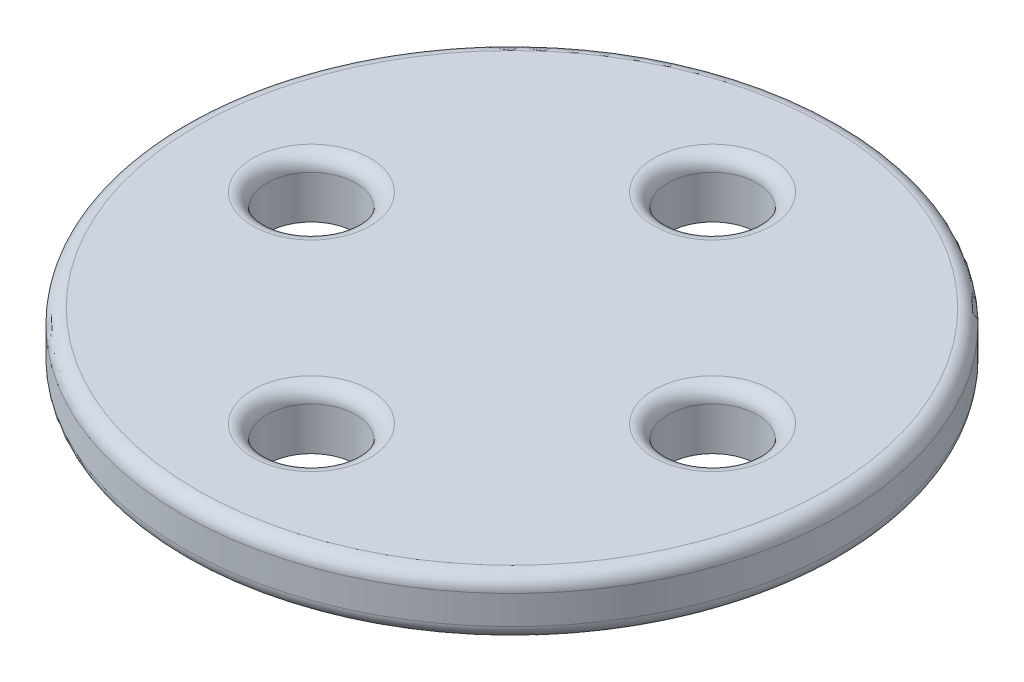
SolidWorks part; units mm, degrees
other "graphite_1"
other "white_2"
other "white_3"
other "white_10"
other "white_7"
other "white_6"
other "blue_2"
ref_plane "Front Plane" through (0, 0, 0) normal (0, 0, 1) x (1, 0, 0)
ref_plane "Top Plane" through (0, 0, 0) normal (0, 1, 0) x (1, 0, 0)
ref_plane "Right Plane" through (0, 0, 0) normal (1, 0, 0) x (0, 0, -1)
sketch "Sketch1" plane through (0, 0, 0) normal (0, 1, 0) x (1, 0, 0)
  line L0 (0, 7) -> (0, 0) construction
  circle A0 centre (0, 0) radius 11.5
  circle A1 centre (0, 7) radius 1.55
  circle A2 centre (7, 0) radius 1.55
  circle A3 centre (0, -7) radius 1.55
  circle A4 centre (-7, 0) radius 1.55
  point P14 (0, 0)
  dimension "D1" = 23
  dimension "D2" = 3.1
  dimension "D3" = 7
  dimension "D4" = 4
extrude "Boss-Extrude1" add sketch "Sketch1" along normal blind 2
fillet "Fillet1" radius 0.5 6 edges at (-7, 2, 1.55) (7, 2, 1.55) (0, 2, 11.5) (0, 2, -5.45) (0, 2, 8.55) (0, 0, 11.5)
sketch "Sketch2" [suppressed] plane through (0, 2, 0) normal (0, 1, 0) x (1, 0, 0)
  line L0 (-2.4749, -2.4749) -> (2.4749, 2.4749) construction
  line L3 (-4.2426, -0.7071) -> (0.7071, 4.2426) construction
  line L4 (-0.7071, -4.2426) -> (4.2426, 0.7071) construction
  line L5 (0, 0) -> (23.072, 0) construction
  line L6 (-6.364, -2.1213) -> (-2.1213, -6.364) construction
  line L7 (-2.1213, -6.364) -> (6.364, 2.1213) construction
  line L8 (6.364, 2.1213) -> (2.1213, 6.364) construction
  line L9 (2.1213, 6.364) -> (-6.364, -2.1213) construction
  line L10 (-6.364, -2.1213) -> (6.364, 2.1213) construction
  line L11 (2.1213, 6.364) -> (6.364, 2.1213)
  line L12 (6.364, 2.1213) -> (4.9497, 0.7071)
  line L13 (2.1213, 6.364) -> (0.7071, 4.9497)
  line L14 (-6.364, -2.1213) -> (-4.9497, -0.7071)
  line L15 (-6.364, -2.1213) -> (-2.1213, -6.364)
  line L16 (-2.1213, -6.364) -> (-0.7071, -4.9497)
  circle A0 centre (-7, 0) radius 2.75 construction
  circle A1 centre (0, 7) radius 2.75 construction
  circle A2 centre (7, 0) radius 2.75 construction
  circle A3 centre (0, -7) radius 2.75 construction
  arc A6 (-4.2426, -0.7071) -> (-0.7071, -4.2426) centre (-2.4749, -2.4749) ccw construction
  arc A7 (4.2426, 0.7071) -> (0.7071, 4.2426) centre (2.4749, 2.4749) ccw construction
  circle A8 centre (0, 0) radius 5 construction
  arc A10 (-0.7071, -4.9497) -> (4.9497, 0.7071) centre (0, 0) ccw
  arc A12 (0.7071, 4.9497) -> (-4.9497, -0.7071) centre (0, 0) ccw
  point P13 (0, 0)
  dimension "D1" = 5.5
  dimension "D2" = 12
  dimension "D3" = 5
  dimension "D7" = 10
  dimension "D4" = 45
  dimension "D5" = 6
  dimension "D6" = 12
extrude "Cable hole" [suppressed] cut sketch "Sketch2" against normal through all
fillet "Fillet2" [suppressed] radius 1
sketch "GL_F_side_blue" plane through (0, 0, 0) normal (0, 1, 0) x (1, 0, 0)
  line L0 (4.1012, -5.7912) -> (3.5426, -5.2326)
  line L1 (3.5426, -5.2326) -> (4.0376, -4.7376)
  line L2 (4.0376, -4.7376) -> (3.7477, -4.4477)
  line L3 (3.7477, -4.4477) -> (3.2527, -4.9427)
  line L4 (3.2527, -4.9427) -> (2.6941, -4.3841)
  line L5 (2.6941, -4.3841) -> (3.1891, -3.8891)
  line L6 (3.1891, -3.8891) -> (1.2092, -1.9092)
  line L7 (1.2092, -1.9092) -> (1.3233, -1.795)
  line L8 (1.3233, -1.795) -> (-1.795, -1.795)
  line L9 (-1.795, -1.795) -> (-1.795, 1.3233)
  line L10 (-1.795, 1.3233) -> (-1.9092, 1.2092)
  line L11 (-1.9092, 1.2092) -> (-4.852, 4.1519)
  line L12 (-4.852, 4.1519) -> (-4.7161, 4.1794)
  line L13 (-4.7161, 4.1794) -> (-4.5701, 4.2398)
  line L14 (-4.5701, 4.2398) -> (-4.3805, 4.3805)
  line L15 (-4.3805, 4.3805) -> (-4.2398, 4.5701)
  line L16 (-4.2398, 4.5701) -> (-4.1794, 4.7161)
  line L17 (-4.1794, 4.7161) -> (-4.1519, 4.852)
  line L18 (-4.1519, 4.852) -> (-1.2092, 1.9092)
  line L19 (-1.2092, 1.9092) -> (-1.3233, 1.795)
  line L20 (-1.3233, 1.795) -> (1.3233, 1.795)
  line L21 (1.3233, 1.795) -> (1.2092, 1.9092)
  line L22 (1.2092, 1.9092) -> (5.6637, 6.3638)
  line L23 (5.6637, 6.3638) -> (5.6872, 6.2571)
  line L24 (5.6872, 6.2571) -> (5.7514, 6.1022)
  line L25 (5.7514, 6.1022) -> (5.9008, 5.9008)
  line L26 (5.9008, 5.9008) -> (6.1022, 5.7514)
  line L27 (6.1022, 5.7514) -> (6.2571, 5.6872)
  line L28 (6.2571, 5.6872) -> (6.3638, 5.6637)
  line L29 (6.3638, 5.6637) -> (1.9092, 1.2092)
  line L30 (1.9092, 1.2092) -> (1.795, 1.3233)
  line L31 (1.795, 1.3233) -> (1.795, -1.3233)
  line L32 (1.795, -1.3233) -> (1.9092, -1.2092)
  line L33 (1.9092, -1.2092) -> (3.8891, -3.1891)
  line L34 (3.8891, -3.1891) -> (4.3841, -2.6941)
  line L35 (4.3841, -2.6941) -> (4.9427, -3.2527)
  line L36 (4.9427, -3.2527) -> (4.4477, -3.7477)
  line L37 (4.4477, -3.7477) -> (4.7376, -4.0376)
  line L38 (4.7376, -4.0376) -> (5.2326, -3.5426)
  line L39 (5.2326, -3.5426) -> (5.7912, -4.1012)
  line L40 (5.7912, -4.1012) -> (5.2962, -4.5962)
  line L41 (5.2962, -4.5962) -> (6.9933, -6.2933)
  line L42 (6.9933, -6.2933) -> (6.2933, -6.9933)
  line L43 (6.2933, -6.9933) -> (4.5962, -5.2962)
  line L44 (4.5962, -5.2962) -> (4.1012, -5.7912)
  line L45 (-0.2962, 0.7941) -> (-0.2962, 0.9029)
  line L46 (-0.2962, 0.9029) -> (-0.3174, 1.0096)
  line L47 (-0.3174, 1.0096) -> (-0.359, 1.1102)
  line L48 (-0.359, 1.1102) -> (-0.4195, 1.2006)
  line L49 (-0.4195, 1.2006) -> (-0.4964, 1.2776)
  line L50 (-0.4964, 1.2776) -> (-0.5869, 1.338)
  line L51 (-0.5869, 1.338) -> (-0.6874, 1.3797)
  line L52 (-0.6874, 1.3797) -> (-0.7941, 1.4009)
  line L53 (-0.7941, 1.4009) -> (-0.9029, 1.4009)
  line L54 (-0.9029, 1.4009) -> (-1.0096, 1.3797)
  line L55 (-1.0096, 1.3797) -> (-1.1102, 1.338)
  line L56 (-1.1102, 1.338) -> (-1.2006, 1.2776)
  line L57 (-1.2006, 1.2776) -> (-1.2776, 1.2006)
  line L58 (-1.2776, 1.2006) -> (-1.338, 1.1102)
  line L59 (-1.338, 1.1102) -> (-1.3797, 1.0096)
  line L60 (-1.3797, 1.0096) -> (-1.4009, 0.9029)
  line L61 (-1.4009, 0.9029) -> (-1.4009, 0.7941)
  line L62 (-1.4009, 0.7941) -> (-1.3797, 0.6874)
  line L63 (-1.3797, 0.6874) -> (-1.338, 0.5869)
  line L64 (-1.338, 0.5869) -> (-1.2776, 0.4964)
  line L65 (-1.2776, 0.4964) -> (-1.2006, 0.4195)
  line L66 (-1.2006, 0.4195) -> (-1.1102, 0.359)
  line L67 (-1.1102, 0.359) -> (-1.0096, 0.3174)
  line L68 (-1.0096, 0.3174) -> (-0.9029, 0.2962)
  line L69 (-0.9029, 0.2962) -> (-0.7941, 0.2962)
  line L70 (-0.7941, 0.2962) -> (-0.6874, 0.3174)
  line L71 (-0.6874, 0.3174) -> (-0.5869, 0.359)
  line L72 (-0.5869, 0.359) -> (-0.4964, 0.4195)
  line L73 (-0.4964, 0.4195) -> (-0.4195, 0.4964)
  line L74 (-0.4195, 0.4964) -> (-0.359, 0.5869)
  line L75 (-0.359, 0.5869) -> (-0.3174, 0.6874)
  line L76 (-0.3174, 0.6874) -> (-0.2962, 0.7941)
extrude "GL_F_side_blue_raised" add sketch "GL_F_side_blue" along normal blind 0.6 from offset 0.6 separate body offset against normal yes
sketch "GL_F_side_white" plane through (0, 0, 0) normal (0, 1, 0) x (1, 0, 0)
  line L0 (-5.628, -6.3839) -> (-5.6958, -6.4665)
  line L1 (-5.6958, -6.4665) -> (-5.7783, -6.5342)
  line L2 (-5.7783, -6.5342) -> (-5.8726, -6.5846)
  line L3 (-5.8726, -6.5846) -> (-5.9748, -6.6156)
  line L4 (-5.9748, -6.6156) -> (-6.0811, -6.6261)
  line L5 (-6.0811, -6.6261) -> (-6.1874, -6.6156)
  line L6 (-6.1874, -6.6156) -> (-6.2897, -6.5846)
  line L7 (-6.2897, -6.5846) -> (-6.3839, -6.5342)
  line L8 (-6.3839, -6.5342) -> (-6.4665, -6.4665)
  line L9 (-6.4665, -6.4665) -> (-6.5342, -6.3839)
  line L10 (-6.5342, -6.3839) -> (-6.5846, -6.2897)
  line L11 (-6.5846, -6.2897) -> (-6.6156, -6.1874)
  line L12 (-6.6156, -6.1874) -> (-6.6261, -6.0811)
  line L13 (-6.6261, -6.0811) -> (-6.6156, -5.9748)
  line L14 (-6.6156, -5.9748) -> (-6.5846, -5.8726)
  line L15 (-6.5846, -5.8726) -> (-6.5342, -5.7783)
  line L16 (-6.5342, -5.7783) -> (-6.4665, -5.6958)
  line L17 (-6.4665, -5.6958) -> (-6.3839, -5.628)
  line L18 (-6.3839, -5.628) -> (-6.2897, -5.5776)
  line L19 (-6.2897, -5.5776) -> (-6.1874, -5.5466)
  line L20 (-6.1874, -5.5466) -> (-6.0811, -5.5361)
  line L21 (-6.0811, -5.5361) -> (-5.9748, -5.5466)
  line L22 (-5.9748, -5.5466) -> (-5.8726, -5.5776)
  line L23 (-5.8726, -5.5776) -> (-5.7783, -5.628)
  line L24 (-5.7783, -5.628) -> (-5.6958, -5.6958)
  line L25 (-5.6958, -5.6958) -> (-5.628, -5.7783)
  line L26 (-5.628, -5.7783) -> (-5.5776, -5.8726)
  line L27 (-5.5776, -5.8726) -> (-5.5466, -5.9748)
  line L28 (-5.5466, -5.9748) -> (-5.5361, -6.0811)
  line L29 (-5.5361, -6.0811) -> (-5.5466, -6.1874)
  line L30 (-5.5466, -6.1874) -> (-5.5776, -6.2897)
  line L31 (-5.5776, -6.2897) -> (-5.628, -6.3839)
  line L32 (-3.7895, -4.5454) -> (-3.8573, -4.628)
  line L33 (-3.8573, -4.628) -> (-3.9399, -4.6958)
  line L34 (-3.9399, -4.6958) -> (-4.0341, -4.7461)
  line L35 (-4.0341, -4.7461) -> (-4.1363, -4.7771)
  line L36 (-4.1363, -4.7771) -> (-4.2426, -4.7876)
  line L37 (-4.2426, -4.7876) -> (-4.349, -4.7771)
  line L38 (-4.349, -4.7771) -> (-4.4512, -4.7461)
  line L39 (-4.4512, -4.7461) -> (-4.5454, -4.6958)
  line L40 (-4.5454, -4.6958) -> (-4.628, -4.628)
  line L41 (-4.628, -4.628) -> (-4.6958, -4.5454)
  line L42 (-4.6958, -4.5454) -> (-4.7461, -4.4512)
  line L43 (-4.7461, -4.4512) -> (-4.7771, -4.349)
  line L44 (-4.7771, -4.349) -> (-4.7876, -4.2426)
  line L45 (-4.7876, -4.2426) -> (-4.7771, -4.1363)
  line L46 (-4.7771, -4.1363) -> (-4.7461, -4.0341)
  line L47 (-4.7461, -4.0341) -> (-4.6958, -3.9399)
  line L48 (-4.6958, -3.9399) -> (-4.628, -3.8573)
  line L49 (-4.628, -3.8573) -> (-4.5454, -3.7895)
  line L50 (-4.5454, -3.7895) -> (-4.4512, -3.7391)
  line L51 (-4.4512, -3.7391) -> (-4.349, -3.7081)
  line L52 (-4.349, -3.7081) -> (-4.2426, -3.6977)
  line L53 (-4.2426, -3.6977) -> (-4.1363, -3.7081)
  line L54 (-4.1363, -3.7081) -> (-4.0341, -3.7391)
  line L55 (-4.0341, -3.7391) -> (-3.9399, -3.7895)
  line L56 (-3.9399, -3.7895) -> (-3.8573, -3.8573)
  line L57 (-3.8573, -3.8573) -> (-3.7895, -3.9399)
  line L58 (-3.7895, -3.9399) -> (-3.7391, -4.0341)
  line L59 (-3.7391, -4.0341) -> (-3.7081, -4.1363)
  line L60 (-3.7081, -4.1363) -> (-3.6977, -4.2426)
  line L61 (-3.6977, -4.2426) -> (-3.7081, -4.349)
  line L62 (-3.7081, -4.349) -> (-3.7391, -4.4512)
  line L63 (-3.7391, -4.4512) -> (-3.7895, -4.5454)
  line L64 (-0.3954, 0.5458) -> (-0.4632, 0.4632)
  line L65 (-0.4632, 0.4632) -> (-0.5458, 0.3954)
  line L66 (-0.5458, 0.3954) -> (-0.64, 0.345)
  line L67 (-0.64, 0.345) -> (-0.7422, 0.314)
  line L68 (-0.7422, 0.314) -> (-0.8485, 0.3036)
  line L69 (-0.8485, 0.3036) -> (-0.9548, 0.314)
  line L70 (-0.9548, 0.314) -> (-1.0571, 0.345)
  line L71 (-1.0571, 0.345) -> (-1.1513, 0.3954)
  line L72 (-1.1513, 0.3954) -> (-1.2339, 0.4632)
  line L73 (-1.2339, 0.4632) -> (-1.3017, 0.5458)
  line L74 (-1.3017, 0.5458) -> (-1.352, 0.64)
  line L75 (-1.352, 0.64) -> (-1.383, 0.7422)
  line L76 (-1.383, 0.7422) -> (-1.3935, 0.8485)
  line L77 (-1.3935, 0.8485) -> (-1.383, 0.9548)
  line L78 (-1.383, 0.9548) -> (-1.352, 1.0571)
  line L79 (-1.352, 1.0571) -> (-1.3017, 1.1513)
  line L80 (-1.3017, 1.1513) -> (-1.2339, 1.2339)
  line L81 (-1.2339, 1.2339) -> (-1.1513, 1.3017)
  line L82 (-1.1513, 1.3017) -> (-1.0571, 1.352)
  line L83 (-1.0571, 1.352) -> (-0.9548, 1.383)
  line L84 (-0.9548, 1.383) -> (-0.8485, 1.3935)
  line L85 (-0.8485, 1.3935) -> (-0.7422, 1.383)
  line L86 (-0.7422, 1.383) -> (-0.64, 1.352)
  line L87 (-0.64, 1.352) -> (-0.5458, 1.3017)
  line L88 (-0.5458, 1.3017) -> (-0.4632, 1.2339)
  line L89 (-0.4632, 1.2339) -> (-0.3954, 1.1513)
  line L90 (-0.3954, 1.1513) -> (-0.345, 1.0571)
  line L91 (-0.345, 1.0571) -> (-0.314, 0.9548)
  line L92 (-0.314, 0.9548) -> (-0.3036, 0.8485)
  line L93 (-0.3036, 0.8485) -> (-0.314, 0.7422)
  line L94 (-0.314, 0.7422) -> (-0.345, 0.64)
  line L95 (-0.345, 0.64) -> (-0.3954, 0.5458)
  line L96 (-4.3876, 4.3876) -> (-4.5081, 4.2887)
  line L97 (-4.5081, 4.2887) -> (-4.6455, 4.2153)
  line L98 (-4.6455, 4.2153) -> (-4.7947, 4.17)
  line L99 (-4.7947, 4.17) -> (-4.9497, 4.1548)
  line L100 (-4.9497, 4.1548) -> (-5.1048, 4.17)
  line L101 (-5.1048, 4.17) -> (-5.254, 4.2153)
  line L102 (-5.254, 4.2153) -> (-5.3914, 4.2887)
  line L103 (-5.3914, 4.2887) -> (-5.5119, 4.3876)
  line L104 (-5.5119, 4.3876) -> (-5.6107, 4.5081)
  line L105 (-5.6107, 4.5081) -> (-5.6842, 4.6455)
  line L106 (-5.6842, 4.6455) -> (-5.7294, 4.7947)
  line L107 (-5.7294, 4.7947) -> (-5.7447, 4.9497)
  line L108 (-5.7447, 4.9497) -> (-5.7294, 5.1048)
  line L109 (-5.7294, 5.1048) -> (-5.6842, 5.254)
  line L110 (-5.6842, 5.254) -> (-5.6107, 5.3914)
  line L111 (-5.6107, 5.3914) -> (-5.5119, 5.5119)
  line L112 (-5.5119, 5.5119) -> (-5.3914, 5.6107)
  line L113 (-5.3914, 5.6107) -> (-5.254, 5.6842)
  line L114 (-5.254, 5.6842) -> (-5.1048, 5.7294)
  line L115 (-5.1048, 5.7294) -> (-4.9497, 5.7447)
  line L116 (-4.9497, 5.7447) -> (-4.7947, 5.7294)
  line L117 (-4.7947, 5.7294) -> (-4.6455, 5.6842)
  line L118 (-4.6455, 5.6842) -> (-4.5081, 5.6107)
  line L119 (-4.5081, 5.6107) -> (-4.3876, 5.5119)
  line L120 (-4.3876, 5.5119) -> (-4.2887, 5.3914)
  line L121 (-4.2887, 5.3914) -> (-4.2153, 5.254)
  line L122 (-4.2153, 5.254) -> (-4.17, 5.1048)
  line L123 (-4.17, 5.1048) -> (-4.1548, 4.9497)
  line L124 (-4.1548, 4.9497) -> (-4.17, 4.7947)
  line L125 (-4.17, 4.7947) -> (-4.2153, 4.6455)
  line L126 (-4.2153, 4.6455) -> (-4.2887, 4.5081)
  line L127 (-4.2887, 4.5081) -> (-4.3876, 4.3876)
  line L128 (7.1029, 5.9079) -> (6.9748, 5.8028)
  line L129 (6.9748, 5.8028) -> (6.8287, 5.7247)
  line L130 (6.8287, 5.7247) -> (6.6702, 5.6766)
  line L131 (6.6702, 5.6766) -> (6.5054, 5.6604)
  line L132 (6.5054, 5.6604) -> (6.3405, 5.6766)
  line L133 (6.3405, 5.6766) -> (6.182, 5.7247)
  line L134 (6.182, 5.7247) -> (6.0359, 5.8028)
  line L135 (6.0359, 5.8028) -> (5.9079, 5.9079)
  line L136 (5.9079, 5.9079) -> (5.8028, 6.0359)
  line L137 (5.8028, 6.0359) -> (5.7247, 6.182)
  line L138 (5.7247, 6.182) -> (5.6766, 6.3405)
  line L139 (5.6766, 6.3405) -> (5.6604, 6.5054)
  line L140 (5.6604, 6.5054) -> (5.6766, 6.6702)
  line L141 (5.6766, 6.6702) -> (5.7247, 6.8287)
  line L142 (5.7247, 6.8287) -> (5.8028, 6.9748)
  line L143 (5.8028, 6.9748) -> (5.9079, 7.1029)
  line L144 (5.9079, 7.1029) -> (6.0359, 7.208)
  line L145 (6.0359, 7.208) -> (6.182, 7.286)
  line L146 (6.182, 7.286) -> (6.3405, 7.3341)
  line L147 (6.3405, 7.3341) -> (6.5054, 7.3504)
  line L148 (6.5054, 7.3504) -> (6.6702, 7.3341)
  line L149 (6.6702, 7.3341) -> (6.8287, 7.286)
  line L150 (6.8287, 7.286) -> (6.9748, 7.208)
  line L151 (6.9748, 7.208) -> (7.1029, 7.1029)
  line L152 (7.1029, 7.1029) -> (7.208, 6.9748)
  line L153 (7.208, 6.9748) -> (7.286, 6.8287)
  line L154 (7.286, 6.8287) -> (7.3341, 6.6702)
  line L155 (7.3341, 6.6702) -> (7.3504, 6.5054)
  line L156 (7.3504, 6.5054) -> (7.3341, 6.3405)
  line L157 (7.3341, 6.3405) -> (7.286, 6.182)
  line L158 (7.286, 6.182) -> (7.208, 6.0359)
  line L159 (7.208, 6.0359) -> (7.1029, 5.9079)
extrude "GL_F_side_white_raised" add sketch "GL_F_side_white" along normal blind 0.6 from offset 0.6 separate body offset against normal yes
sketch "GL_E_side_blue" plane through (0, 0, 0) normal (0, 1, 0) x (1, 0, 0)
  line L0 (4.3841, -6.074) -> (3.8254, -5.5154)
  line L1 (3.8254, -5.5154) -> (4.3204, -5.0205)
  line L2 (4.3204, -5.0205) -> (4.0305, -4.7305)
  line L3 (4.0305, -4.7305) -> (3.5355, -5.2255)
  line L4 (3.5355, -5.2255) -> (2.9769, -4.6669)
  line L5 (2.9769, -4.6669) -> (3.4719, -4.1719)
  line L6 (3.4719, -4.1719) -> (3.182, -3.882)
  line L7 (3.182, -3.882) -> (2.687, -4.377)
  line L8 (2.687, -4.377) -> (2.1284, -3.8184)
  line L9 (2.1284, -3.8184) -> (2.6234, -3.3234)
  line L10 (2.6234, -3.3234) -> (0.8839, -1.5839)
  line L11 (0.8839, -1.5839) -> (0, -2.4678)
  line L12 (0, -2.4678) -> (-0.8839, -1.5839)
  line L13 (-0.8839, -1.5839) -> (-3.4994, -4.1994)
  line L14 (-3.4994, -4.1994) -> (-3.7618, -5.6882)
  line L15 (-3.7618, -5.6882) -> (-3.8485, -5.6032)
  line L16 (-3.8485, -5.6032) -> (-3.9798, -5.5155)
  line L17 (-3.9798, -5.5155) -> (-4.202, -5.436)
  line L18 (-4.202, -5.436) -> (-4.3592, -5.4205)
  line L19 (-4.3592, -5.4205) -> (-4.5164, -5.436)
  line L20 (-4.5164, -5.436) -> (-4.7368, -5.5165)
  line L21 (-4.7368, -5.5165) -> (-4.4202, -3.7202)
  line L22 (-4.4202, -3.7202) -> (-1.5839, -0.8839)
  line L23 (-1.5839, -0.8839) -> (-2.4678, 0)
  line L24 (-2.4678, 0) -> (0, 2.4678)
  line L25 (0, 2.4678) -> (0.8839, 1.5839)
  line L26 (0.8839, 1.5839) -> (5.5223, 6.2223)
  line L27 (5.5223, 6.2223) -> (5.5458, 6.1157)
  line L28 (5.5458, 6.1157) -> (5.6099, 5.9608)
  line L29 (5.6099, 5.9608) -> (5.7593, 5.7593)
  line L30 (5.7593, 5.7593) -> (5.9608, 5.6099)
  line L31 (5.9608, 5.6099) -> (6.1157, 5.5458)
  line L32 (6.1157, 5.5458) -> (6.2223, 5.5223)
  line L33 (6.2223, 5.5223) -> (1.5839, 0.8839)
  line L34 (1.5839, 0.8839) -> (2.4678, 0)
  line L35 (2.4678, 0) -> (1.5839, -0.8839)
  line L36 (1.5839, -0.8839) -> (3.3234, -2.6234)
  line L37 (3.3234, -2.6234) -> (3.8184, -2.1284)
  line L38 (3.8184, -2.1284) -> (4.377, -2.687)
  line L39 (4.377, -2.687) -> (3.882, -3.182)
  line L40 (3.882, -3.182) -> (4.1719, -3.4719)
  line L41 (4.1719, -3.4719) -> (4.6669, -2.9769)
  line L42 (4.6669, -2.9769) -> (5.2255, -3.5355)
  line L43 (5.2255, -3.5355) -> (4.7305, -4.0305)
  line L44 (4.7305, -4.0305) -> (5.0205, -4.3204)
  line L45 (5.0205, -4.3204) -> (5.5154, -3.8254)
  line L46 (5.5154, -3.8254) -> (6.074, -4.3841)
  line L47 (6.074, -4.3841) -> (5.5791, -4.879)
  line L48 (5.5791, -4.879) -> (7.1347, -6.4347)
  line L49 (7.1347, -6.4347) -> (6.4347, -7.1347)
  line L50 (6.4347, -7.1347) -> (4.879, -5.5791)
  line L51 (4.879, -5.5791) -> (4.3841, -6.074)
  line L52 (0.5524, 0.9456) -> (0.5524, 1.0544)
  line L53 (0.5524, 1.0544) -> (0.5311, 1.1611)
  line L54 (0.5311, 1.1611) -> (0.4895, 1.2616)
  line L55 (0.4895, 1.2616) -> (0.429, 1.3521)
  line L56 (0.429, 1.3521) -> (0.3521, 1.429)
  line L57 (0.3521, 1.429) -> (0.2616, 1.4895)
  line L58 (0.2616, 1.4895) -> (0.1611, 1.5311)
  line L59 (0.1611, 1.5311) -> (0.0544, 1.5524)
  line L60 (0.0544, 1.5524) -> (-0.0544, 1.5524)
  line L61 (-0.0544, 1.5524) -> (-0.1611, 1.5311)
  line L62 (-0.1611, 1.5311) -> (-0.2616, 1.4895)
  line L63 (-0.2616, 1.4895) -> (-0.3521, 1.429)
  line L64 (-0.3521, 1.429) -> (-0.429, 1.3521)
  line L65 (-0.429, 1.3521) -> (-0.4895, 1.2616)
  line L66 (-0.4895, 1.2616) -> (-0.5311, 1.1611)
  line L67 (-0.5311, 1.1611) -> (-0.5524, 1.0544)
  line L68 (-0.5524, 1.0544) -> (-0.5524, 0.9456)
  line L69 (-0.5524, 0.9456) -> (-0.5311, 0.8389)
  line L70 (-0.5311, 0.8389) -> (-0.4895, 0.7384)
  line L71 (-0.4895, 0.7384) -> (-0.429, 0.6479)
  line L72 (-0.429, 0.6479) -> (-0.3521, 0.571)
  line L73 (-0.3521, 0.571) -> (-0.2616, 0.5105)
  line L74 (-0.2616, 0.5105) -> (-0.1611, 0.4689)
  line L75 (-0.1611, 0.4689) -> (-0.0544, 0.4476)
  line L76 (-0.0544, 0.4476) -> (0.0544, 0.4476)
  line L77 (0.0544, 0.4476) -> (0.1611, 0.4689)
  line L78 (0.1611, 0.4689) -> (0.2616, 0.5105)
  line L79 (0.2616, 0.5105) -> (0.3521, 0.571)
  line L80 (0.3521, 0.571) -> (0.429, 0.6479)
  line L81 (0.429, 0.6479) -> (0.4895, 0.7384)
  line L82 (0.4895, 0.7384) -> (0.5311, 0.8389)
  line L83 (0.5311, 0.8389) -> (0.5524, 0.9456)
extrude "GL_E_side_blue_raised" [suppressed] add sketch "GL_E_side_blue" along normal blind 0.6 from offset 2 separate body
sketch "GL_E_side_white" plane through (0, 0, 0) normal (0, 1, 0) x (1, 0, 0)
  line L0 (-3.6982, -6.6672) -> (-3.797, -6.7877)
  line L1 (-3.797, -6.7877) -> (-3.9175, -6.8866)
  line L2 (-3.9175, -6.8866) -> (-4.055, -6.96)
  line L3 (-4.055, -6.96) -> (-4.2041, -7.0053)
  line L4 (-4.2041, -7.0053) -> (-4.3592, -7.0205)
  line L5 (-4.3592, -7.0205) -> (-4.5143, -7.0053)
  line L6 (-4.5143, -7.0053) -> (-4.6634, -6.96)
  line L7 (-4.6634, -6.96) -> (-4.8008, -6.8866)
  line L8 (-4.8008, -6.8866) -> (-4.9213, -6.7877)
  line L9 (-4.9213, -6.7877) -> (-5.0202, -6.6672)
  line L10 (-5.0202, -6.6672) -> (-5.0936, -6.5298)
  line L11 (-5.0936, -6.5298) -> (-5.1389, -6.3806)
  line L12 (-5.1389, -6.3806) -> (-5.1542, -6.2256)
  line L13 (-5.1542, -6.2256) -> (-5.1389, -6.0705)
  line L14 (-5.1389, -6.0705) -> (-5.0936, -5.9213)
  line L15 (-5.0936, -5.9213) -> (-5.0202, -5.7839)
  line L16 (-5.0202, -5.7839) -> (-4.9213, -5.6634)
  line L17 (-4.9213, -5.6634) -> (-4.8008, -5.5646)
  line L18 (-4.8008, -5.5646) -> (-4.6634, -5.4911)
  line L19 (-4.6634, -5.4911) -> (-4.5143, -5.4459)
  line L20 (-4.5143, -5.4459) -> (-4.3592, -5.4306)
  line L21 (-4.3592, -5.4306) -> (-4.2041, -5.4459)
  line L22 (-4.2041, -5.4459) -> (-4.055, -5.4911)
  line L23 (-4.055, -5.4911) -> (-3.9175, -5.5646)
  line L24 (-3.9175, -5.5646) -> (-3.797, -5.6634)
  line L25 (-3.797, -5.6634) -> (-3.6982, -5.7839)
  line L26 (-3.6982, -5.7839) -> (-3.6247, -5.9213)
  line L27 (-3.6247, -5.9213) -> (-3.5795, -6.0705)
  line L28 (-3.5795, -6.0705) -> (-3.5642, -6.2256)
  line L29 (-3.5642, -6.2256) -> (-3.5795, -6.3806)
  line L30 (-3.5795, -6.3806) -> (-3.6247, -6.5298)
  line L31 (-3.6247, -6.5298) -> (-3.6982, -6.6672)
  line L32 (0.4531, 0.6972) -> (0.3854, 0.6146)
  line L33 (0.3854, 0.6146) -> (0.3028, 0.5469)
  line L34 (0.3028, 0.5469) -> (0.2086, 0.4965)
  line L35 (0.2086, 0.4965) -> (0.1063, 0.4655)
  line L36 (0.1063, 0.4655) -> (0, 0.455)
  line L37 (0, 0.455) -> (-0.1063, 0.4655)
  line L38 (-0.1063, 0.4655) -> (-0.2086, 0.4965)
  line L39 (-0.2086, 0.4965) -> (-0.3028, 0.5469)
  line L40 (-0.3028, 0.5469) -> (-0.3854, 0.6146)
  line L41 (-0.3854, 0.6146) -> (-0.4531, 0.6972)
  line L42 (-0.4531, 0.6972) -> (-0.5035, 0.7914)
  line L43 (-0.5035, 0.7914) -> (-0.5345, 0.8937)
  line L44 (-0.5345, 0.8937) -> (-0.545, 1)
  line L45 (-0.545, 1) -> (-0.5345, 1.1063)
  line L46 (-0.5345, 1.1063) -> (-0.5035, 1.2086)
  line L47 (-0.5035, 1.2086) -> (-0.4531, 1.3028)
  line L48 (-0.4531, 1.3028) -> (-0.3854, 1.3854)
  line L49 (-0.3854, 1.3854) -> (-0.3028, 1.4531)
  line L50 (-0.3028, 1.4531) -> (-0.2086, 1.5035)
  line L51 (-0.2086, 1.5035) -> (-0.1063, 1.5345)
  line L52 (-0.1063, 1.5345) -> (0, 1.545)
  line L53 (0, 1.545) -> (0.1063, 1.5345)
  line L54 (0.1063, 1.5345) -> (0.2086, 1.5035)
  line L55 (0.2086, 1.5035) -> (0.3028, 1.4531)
  line L56 (0.3028, 1.4531) -> (0.3854, 1.3854)
  line L57 (0.3854, 1.3854) -> (0.4531, 1.3028)
  line L58 (0.4531, 1.3028) -> (0.5035, 1.2086)
  line L59 (0.5035, 1.2086) -> (0.5345, 1.1063)
  line L60 (0.5345, 1.1063) -> (0.545, 1)
  line L61 (0.545, 1) -> (0.5345, 0.8937)
  line L62 (0.5345, 0.8937) -> (0.5035, 0.7914)
  line L63 (0.5035, 0.7914) -> (0.4531, 0.6972)
  line L64 (-3.9309, 4.0813) -> (-3.9987, 3.9987)
  line L65 (-3.9987, 3.9987) -> (-4.0813, 3.9309)
  line L66 (-4.0813, 3.9309) -> (-4.1755, 3.8806)
  line L67 (-4.1755, 3.8806) -> (-4.2777, 3.8496)
  line L68 (-4.2777, 3.8496) -> (-4.3841, 3.8391)
  line L69 (-4.3841, 3.8391) -> (-4.4904, 3.8496)
  line L70 (-4.4904, 3.8496) -> (-4.5926, 3.8806)
  line L71 (-4.5926, 3.8806) -> (-4.6868, 3.9309)
  line L72 (-4.6868, 3.9309) -> (-4.7694, 3.9987)
  line L73 (-4.7694, 3.9987) -> (-4.8372, 4.0813)
  line L74 (-4.8372, 4.0813) -> (-4.8876, 4.1755)
  line L75 (-4.8876, 4.1755) -> (-4.9186, 4.2777)
  line L76 (-4.9186, 4.2777) -> (-4.929, 4.3841)
  line L77 (-4.929, 4.3841) -> (-4.9186, 4.4904)
  line L78 (-4.9186, 4.4904) -> (-4.8876, 4.5926)
  line L79 (-4.8876, 4.5926) -> (-4.8372, 4.6868)
  line L80 (-4.8372, 4.6868) -> (-4.7694, 4.7694)
  line L81 (-4.7694, 4.7694) -> (-4.6868, 4.8372)
  line L82 (-4.6868, 4.8372) -> (-4.5926, 4.8876)
  line L83 (-4.5926, 4.8876) -> (-4.4904, 4.9186)
  line L84 (-4.4904, 4.9186) -> (-4.3841, 4.929)
  line L85 (-4.3841, 4.929) -> (-4.2777, 4.9186)
  line L86 (-4.2777, 4.9186) -> (-4.1755, 4.8876)
  line L87 (-4.1755, 4.8876) -> (-4.0813, 4.8372)
  line L88 (-4.0813, 4.8372) -> (-3.9987, 4.7694)
  line L89 (-3.9987, 4.7694) -> (-3.9309, 4.6868)
  line L90 (-3.9309, 4.6868) -> (-3.8806, 4.5926)
  line L91 (-3.8806, 4.5926) -> (-3.8496, 4.4904)
  line L92 (-3.8496, 4.4904) -> (-3.8391, 4.3841)
  line L93 (-3.8391, 4.3841) -> (-3.8496, 4.2777)
  line L94 (-3.8496, 4.2777) -> (-3.8806, 4.1755)
  line L95 (-3.8806, 4.1755) -> (-3.9309, 4.0813)
  line L96 (-5.519, 5.519) -> (-5.6091, 5.445)
  line L97 (-5.6091, 5.445) -> (-5.712, 5.39)
  line L98 (-5.712, 5.39) -> (-5.8236, 5.3562)
  line L99 (-5.8236, 5.3562) -> (-5.9397, 5.3447)
  line L100 (-5.9397, 5.3447) -> (-6.0558, 5.3562)
  line L101 (-6.0558, 5.3562) -> (-6.1674, 5.39)
  line L102 (-6.1674, 5.39) -> (-6.2702, 5.445)
  line L103 (-6.2702, 5.445) -> (-6.3604, 5.519)
  line L104 (-6.3604, 5.519) -> (-6.4344, 5.6091)
  line L105 (-6.4344, 5.6091) -> (-6.4894, 5.712)
  line L106 (-6.4894, 5.712) -> (-6.5232, 5.8236)
  line L107 (-6.5232, 5.8236) -> (-6.5347, 5.9397)
  line L108 (-6.5347, 5.9397) -> (-6.5232, 6.0558)
  line L109 (-6.5232, 6.0558) -> (-6.4894, 6.1674)
  line L110 (-6.4894, 6.1674) -> (-6.4344, 6.2702)
  line L111 (-6.4344, 6.2702) -> (-6.3604, 6.3604)
  line L112 (-6.3604, 6.3604) -> (-6.2702, 6.4344)
  line L113 (-6.2702, 6.4344) -> (-6.1674, 6.4894)
  line L114 (-6.1674, 6.4894) -> (-6.0558, 6.5232)
  line L115 (-6.0558, 6.5232) -> (-5.9397, 6.5347)
  line L116 (-5.9397, 6.5347) -> (-5.8236, 6.5232)
  line L117 (-5.8236, 6.5232) -> (-5.712, 6.4894)
  line L118 (-5.712, 6.4894) -> (-5.6091, 6.4344)
  line L119 (-5.6091, 6.4344) -> (-5.519, 6.3604)
  line L120 (-5.519, 6.3604) -> (-5.445, 6.2702)
  line L121 (-5.445, 6.2702) -> (-5.39, 6.1674)
  line L122 (-5.39, 6.1674) -> (-5.3562, 6.0558)
  line L123 (-5.3562, 6.0558) -> (-5.3447, 5.9397)
  line L124 (-5.3447, 5.9397) -> (-5.3562, 5.8236)
  line L125 (-5.3562, 5.8236) -> (-5.39, 5.712)
  line L126 (-5.39, 5.712) -> (-5.445, 5.6091)
  line L127 (-5.445, 5.6091) -> (-5.519, 5.519)
  line L128 (6.9614, 5.7665) -> (6.8334, 5.6614)
  line L129 (6.8334, 5.6614) -> (6.6873, 5.5833)
  line L130 (6.6873, 5.5833) -> (6.5288, 5.5352)
  line L131 (6.5288, 5.5352) -> (6.364, 5.519)
  line L132 (6.364, 5.519) -> (6.1991, 5.5352)
  line L133 (6.1991, 5.5352) -> (6.0406, 5.5833)
  line L134 (6.0406, 5.5833) -> (5.8945, 5.6614)
  line L135 (5.8945, 5.6614) -> (5.7665, 5.7665)
  line L136 (5.7665, 5.7665) -> (5.6614, 5.8945)
  line L137 (5.6614, 5.8945) -> (5.5833, 6.0406)
  line L138 (5.5833, 6.0406) -> (5.5352, 6.1991)
  line L139 (5.5352, 6.1991) -> (5.519, 6.364)
  line L140 (5.519, 6.364) -> (5.5352, 6.5288)
  line L141 (5.5352, 6.5288) -> (5.5833, 6.6873)
  line L142 (5.5833, 6.6873) -> (5.6614, 6.8334)
  line L143 (5.6614, 6.8334) -> (5.7665, 6.9614)
  line L144 (5.7665, 6.9614) -> (5.8945, 7.0665)
  line L145 (5.8945, 7.0665) -> (6.0406, 7.1446)
  line L146 (6.0406, 7.1446) -> (6.1991, 7.1927)
  line L147 (6.1991, 7.1927) -> (6.364, 7.2089)
  line L148 (6.364, 7.2089) -> (6.5288, 7.1927)
  line L149 (6.5288, 7.1927) -> (6.6873, 7.1446)
  line L150 (6.6873, 7.1446) -> (6.8334, 7.0665)
  line L151 (6.8334, 7.0665) -> (6.9614, 6.9614)
  line L152 (6.9614, 6.9614) -> (7.0665, 6.8334)
  line L153 (7.0665, 6.8334) -> (7.1446, 6.6873)
  line L154 (7.1446, 6.6873) -> (7.1927, 6.5288)
  line L155 (7.1927, 6.5288) -> (7.2089, 6.364)
  line L156 (7.2089, 6.364) -> (7.1927, 6.1991)
  line L157 (7.1927, 6.1991) -> (7.1446, 6.0406)
  line L158 (7.1446, 6.0406) -> (7.0665, 5.8945)
  line L159 (7.0665, 5.8945) -> (6.9614, 5.7665)
extrude "GL_E_side_white_raised" [suppressed] add sketch "GL_E_side_white" along normal blind 0.6 from offset 2 separate body
